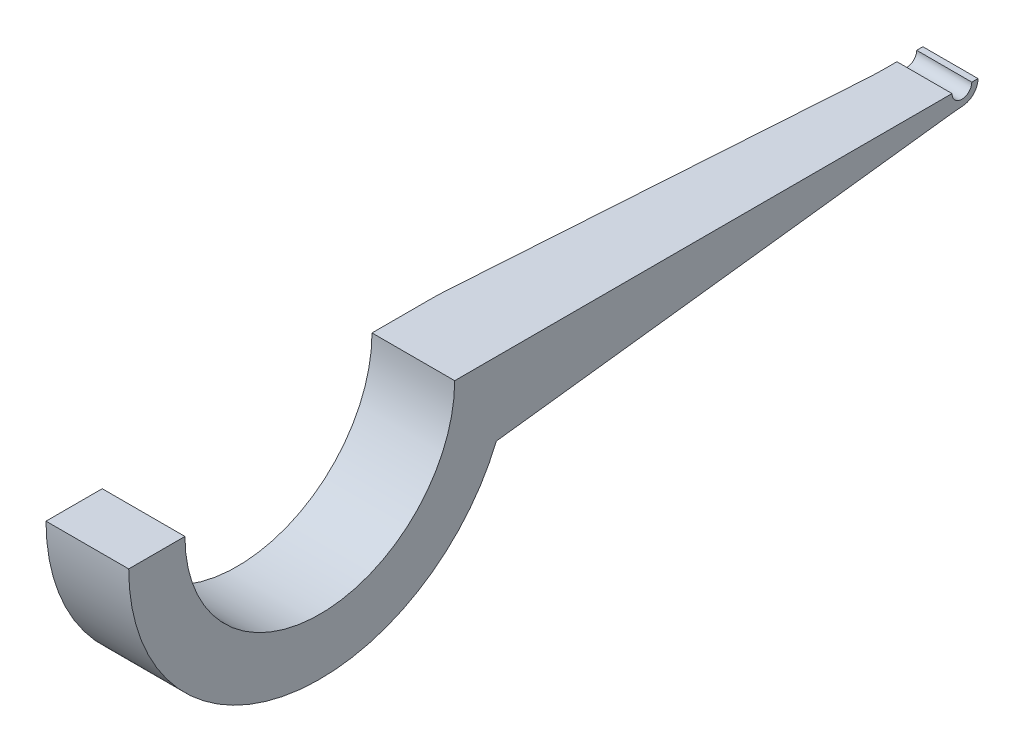
SolidWorks part; units mm, degrees
ref_plane "Front Plane" through (0, 0, 0) normal (1, 0, 0) x (0, 1, 0)
ref_plane "Top Plane" through (0, 0, 0) normal (0, 0, 1) x (0, 1, 0)
ref_plane "Right Plane" through (0, 0, 0) normal (0, 1, 0) x (-1, 0, 0)
sketch "Rim Base" plane through (1321.9127, 0, 0) normal (-1, 0, 0) x (0, -1, 0)
  line L0 (-601.9127, 917.067) -> (-621.8122, 869.0252) construction
  line L1 (-601.9127, 742.367) -> (-601.9127, 737.992)
  line L2 (-601.9127, 737.992) -> (-601.9127, 737.592) construction
  line L3 (-601.9127, 917.067) -> (-582.0132, 869.0252) construction
  line L4 (-601.9127, 917.067) -> (-601.9127, 742.367)
  line L5 (-621.8122, 869.0252) -> (-606.8221, 747.1987)
  line L6 (-582.0132, 869.0252) -> (-597.0033, 747.1987)
  line L7 (-607.2191, 747.1498) -> (-606.8221, 747.1987) construction
  line L8 (-601.9127, 917.067) -> (-601.9127, 969.067)
  circle A0 centre (-601.9127, 742.367) radius 2.6892
  circle A1 centre (-601.9127, 742.367) radius 2.4892 construction
  circle A2 centre (-601.9127, 742.367) radius 4.375
  arc A3 (-616.6077, 738.1946) -> (-587.2177, 738.1946) centre (-601.9127, 917.067) ccw construction
  arc A4 (-616.6077, 738.1946) -> (-587.2177, 738.1946) centre (-601.9127, 917.067) ccw construction
  circle A5 centre (-601.9127, 1091.767) radius 2.4892 construction
  circle A6 centre (-601.9127, 1091.767) radius 2.4892
  circle A7 centre (-601.9127, 917.067) radius 36.7
  circle A8 centre (-605.6062, 911.2051) radius 36.5 construction
  circle A9 centre (-605.6062, 911.2051) radius 36.5 construction
  circle A10 centre (-601.9127, 917.067) radius 36.5
  circle A11 centre (-601.9127, 917.067) radius 52
  arc A12 (-561.6779, 939.0315) -> (-603.4719, 963.1613) centre (-605.6062, 911.2051) ccw construction
  arc A13 (-606.8221, 747.1987) -> (-606.2707, 741.9818) centre (-758.7804, 728.5009) cw
  arc A14 (-597.0033, 747.1987) -> (-597.5547, 741.9818) centre (-445.045, 728.5009) ccw
  arc M9 (-592.0897, 747.351) -> (-611.7357, 747.351) centre (-601.9127, 917.067) cw
  dimension "D1" = 0.2
  dimension "D2" = 0.4
  dimension "D3" = 0.2
  dimension "D5" = 22.5
  dimension "D6" = 0.4
extrude "Boss-Extrude1" add sketch "Rim Base" along normal blind 22.5 contours A14 L6 A11 L4 M9 | L4 A11 L8 A7 | L1 A2 L4 A0 | A14 L4 A2 M9 region at (1321.9127, 599.942, 740.3962) region at (1321.9127, 598.5602, 745.9732) region at (1321.9127, 594.9772, 818.6466) region at (1321.9127, 600.7499, 872.717)
ref_axis "Axis1" through (1299.4127, 601.9127, 917.067) along (1, 0, 0)
ref_axis "Axis2" through (1299.4127, 601.9127, 742.367) along (1, 0, 0)
ref_plane "Plane1" through (0, 601.9127, 0) normal (0, 1, 0) x (1, 0, 0)
sketch "Sketch1" plane through (0, 601.9127, 0) normal (0, 1, 0) x (1, 0, 0)
  line L0 (1321.9127, -865.067) -> (1299.4127, -865.067)
  line L1 (1321.9127, -880.367) -> (1321.9127, -745.0562) construction
  line L2 (1299.4127, -880.367) -> (1299.4127, -745.0562) construction
  line L3 (1299.4127, -737.992) -> (1321.9127, -737.992)
  line L4 (1299.4127, -739.6778) -> (1299.4127, -745.0562) construction
  line L5 (1299.4127, -739.6778) -> (1299.4127, -737.992) construction
  line L6 (1299.4127, -880.367) -> (1299.4127, -745.0562)
  line L7 (1306.9127, -737.992) -> (1306.9127, -747.992)
  line L8 (1299.4127, -737.992) -> (1321.9127, -737.992) construction
  line L9 (1306.733, -753.351) -> (1299.5924, -859.708)
  line L10 (1299.4127, -739.6778) -> (1299.4127, -745.0562)
  line L11 (1299.4127, -739.6778) -> (1299.4127, -737.992)
  arc A0 (1306.9127, -747.992) -> (1306.733, -753.351) centre (1226.9127, -747.992) cw
  arc A1 (1299.5924, -859.708) -> (1299.4127, -865.067) centre (1379.4127, -865.067) ccw
  point P10 (1302.8533, -834.7173)
  point P16 (0, 0)
  point P17 (1303.7965, -833.5107)
  point P19 (1313.8156, -747.6958)
  dimension "D3" = 80
  dimension "D1" = 15
  dimension "D2" = 10
revolve "Cut-Revolve1" cut sketch "Sketch1" angle 360 about axis through (1299.4127, 601.9127, 917.067) along (1, 0, 0) region at (1302.1429, 601.9127, 779.8647)
equation "\"tol\"= 0.2mm"
